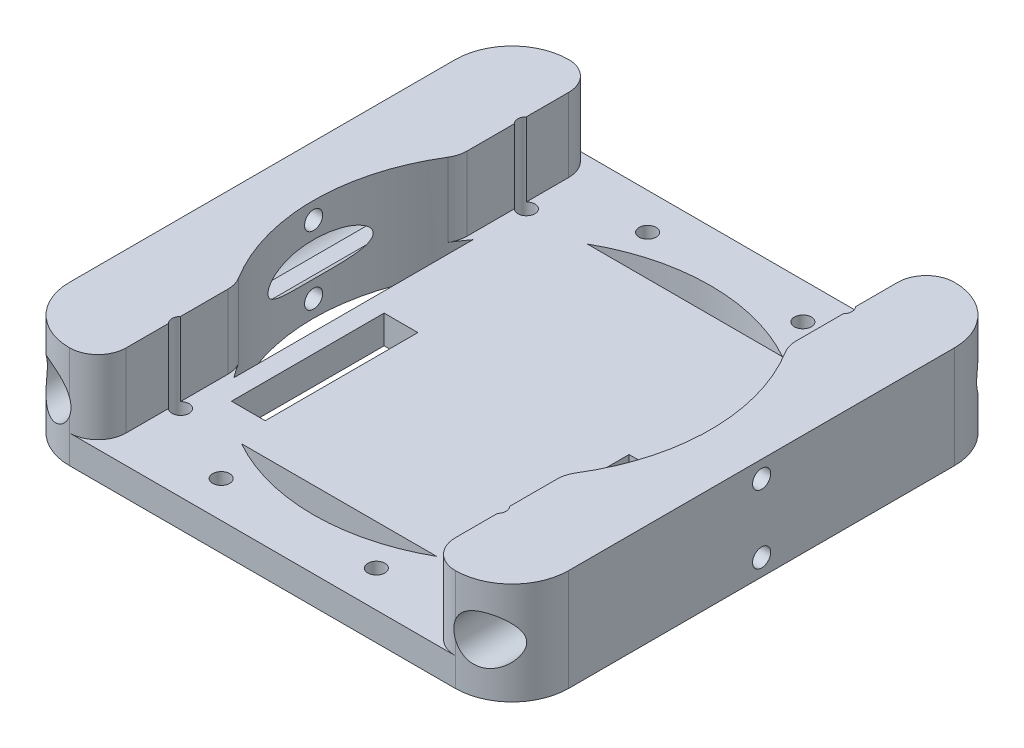
SolidWorks part; units mm, degrees
ref_plane "Front Plane" through (0, 0, 0) normal (0, 0, 1) x (1, 0, 0)
ref_plane "Top Plane" through (0, 0, 0) normal (0, 1, 0) x (1, 0, 0)
ref_plane "Right Plane" through (0, 0, 0) normal (1, 0, 0) x (0, 0, -1)
sketch "Sketch1" plane through (0, 0, 0) normal (0, 1, 0) x (1, 0, 0)
  line L0 (-44, 0) -> (-44, -44) construction
  line L1 (-44, -44) -> (44, -44) construction
  line L2 (44, -44) -> (44, 0) construction
  line L4 (-44, -44) -> (44, -44)
  line L5 (-44, -44) -> (-44, 44)
  line L6 (-44, 44) -> (44, 44)
  line L7 (44, -44) -> (44, 44)
  arc A0 (44, 0) -> (-44, 0) centre (0, 0) ccw construction
  dimension "D1" = 88
extrude "Boss-Extrude1" add sketch "Sketch1" along normal blind 18
sketch "Sketch2" plane through (0, 0, 44) normal (0, 0, 1) x (1, 0, 0)
  line L1 (-1044, 9) -> (48956, 9) construction
  line L2 (0, -1000) -> (0, 49000) construction
  line L3 (-44, 18) -> (-44, 0) construction
  circle A0 centre (-38, 9) radius 4.25
  circle A1 centre (38, 9) radius 4.25
  point P7 (-44, 9)
  dimension "D1" = 8.5
  dimension "D2" = 6
extrude "Cut-Extrude1" cut sketch "Sketch2" against normal through all
fillet "Fillet1" radius 10 4 edges at (44, 9, 44) (-44, 9, 44) (44, 9, -44) (-44, 9, -44)
sketch "Sketch3" plane through (0, 18, 0) normal (0, 1, 0) x (1, 0, 0)
  circle A0 centre (0, 0) radius 35
  dimension "D1" = 70
extrude "Cut-Extrude2" cut sketch "Sketch3" against normal through all
sketch "Sketch5" plane through (0, 0, 0) normal (0, 1, 0) x (1, 0, 0)
  line L0 (-44, 34) -> (-44, -34) construction
  circle A0 centre (0, 0) radius 44
  circle A1 centre (0, 0) radius 35
  circle A3 centre (0, 0) radius 35 construction
extrude "Boss-Extrude2" add sketch "Sketch5" along normal blind 5
sketch "Sketch8" plane through (0, 18, 0) normal (0, 1, 0) x (1, 0, 0)
  line L0 (-34, -44) -> (34, -44) construction
  line L1 (29, 46) -> (-29, 46)
  line L2 (29, 46) -> (29, -46)
  line L3 (29, -46) -> (-29, -46)
  line L4 (-29, 46) -> (-29, -46)
  line L5 (29, 46) -> (-29, -46) construction
  line L6 (29, -46) -> (-29, 46) construction
  point P0 (0, 0)
  point P8 (28.1766, -10.94)
  point P9 (40.6366, 4.14)
  point P11 (0, 0)
  dimension "D1" = 58
  dimension "D2" = 2
extrude "Cut-Extrude4" cut sketch "Sketch8" against normal up to surface (13 mm away) up to face at (-38.0405, 5, 0)
fillet "Fillet2" radius 5 8 edges at (29, 11.5, 44) (29, 11.5, 19.5959) (29, 11.5, -19.5959) (29, 11.5, -44) (-29, 11.5, -44) (-29, 11.5, -19.5959) (-29, 11.5, 19.5959) (-29, 11.5, 44)
sketch "Sketch10" plane through (0, 5, 0) normal (0, 1, 0) x (1, 0, 0)
  line L1 (27.94, -30.48) -> (-27.94, -30.48)
  line L2 (27.94, -30.48) -> (27.94, 30.48)
  line L3 (27.94, 30.48) -> (-27.94, 30.48)
  line L4 (-27.94, -30.48) -> (-27.94, 30.48)
  line L5 (27.94, -30.48) -> (-27.94, 30.48) construction
  line L6 (27.94, 30.48) -> (-27.94, -30.48) construction
  line L7 (-19.12, -24.38) -> (-24.07, -24.38)
  line L8 (-19.12, -24.38) -> (-19.12, 1.53)
  line L9 (-19.12, 1.53) -> (-24.07, 1.53)
  line L10 (-24.07, -24.38) -> (-24.07, 1.53)
  line L11 (-19.12, -24.38) -> (-24.07, 1.53) construction
  line L12 (-19.12, 1.53) -> (-24.07, -24.38) construction
  line L13 (24.06, -24.38) -> (19.11, -24.38)
  line L14 (24.06, -24.38) -> (24.06, 1.53)
  line L15 (24.06, 1.53) -> (19.11, 1.53)
  line L16 (19.11, -24.38) -> (19.11, 1.53)
  line L17 (24.06, -24.38) -> (19.11, 1.53) construction
  line L18 (24.06, 1.53) -> (19.11, -24.38) construction
  point P0 (0, 0)
  point P6 (21.585, -11.425)
  point P7 (-21.595, -11.425)
  dimension "D1" = 55.88
  dimension "D2" = 60.96
  dimension "D3" = 3.87
  dimension "D4" = 4.95
  dimension "D5" = 25.91
  dimension "D6" = 38.23
  dimension "D7" = 6.1
extrude "Boss-Extrude3" add sketch "Sketch10" against normal up to surface (5 mm away) up to face at (0, 0, 0)
sketch "Sketch11" plane through (0, 5, 0) normal (0, 1, 0) x (1, 0, 0)
  line L0 (18.61, 2.03) -> (18.61, -24.88)
  line L1 (-24.07, 1.53) -> (-19.12, 1.53) construction
  line L2 (-24.07, 1.53) -> (-24.07, -24.38) construction
  line L3 (-24.07, -24.38) -> (-19.12, -24.38) construction
  line L4 (-19.12, 1.53) -> (-19.12, -24.38) construction
  line L5 (24.06, 1.53) -> (19.11, 1.53) construction
  line L6 (24.06, 1.53) -> (24.06, -24.38) construction
  line L7 (24.06, -24.38) -> (19.11, -24.38) construction
  line L8 (19.11, 1.53) -> (19.11, -24.38) construction
  line L9 (24.56, -24.88) -> (18.61, -24.88)
  line L10 (24.56, 2.03) -> (24.56, -24.88)
  line L11 (24.56, 2.03) -> (18.61, 2.03)
  line L12 (-24.57, -24.88) -> (-18.62, -24.88)
  line L13 (-18.62, 2.03) -> (-18.62, -24.88)
  line L14 (-24.57, 2.03) -> (-18.62, 2.03)
  line L15 (-24.57, 2.03) -> (-24.57, -24.88)
  line L16 (17.2038, 30.48) -> (-17.2038, 30.48) construction
  line L17 (27.94, -30.48) -> (-27.94, -30.48) construction
  line L18 (27.94, -30.48) -> (27.94, 30.48) construction
  line L19 (27.94, 30.48) -> (-27.94, 30.48) construction
  line L20 (-27.94, -30.48) -> (-27.94, 30.48) construction
  line L21 (27.94, -30.48) -> (-27.94, 30.48) construction
  line L22 (27.94, 30.48) -> (-27.94, -30.48) construction
  line L23 (-27.94, 21.0798) -> (-27.94, -21.0798) construction
  circle A0 centre (-27.94, 30.48) radius 1.5
  circle A1 centre (27.94, 30.48) radius 1.5
  circle A2 centre (-27.94, -30.48) radius 1.5
  circle A3 centre (27.94, -30.48) radius 1.5
  point P20 (0, 0)
  dimension "D3" = 3
  dimension "D1" = 0.5
  dimension "D2" = 0.5
extrude "Cut-Extrude5" cut sketch "Sketch11" against normal through all and the other way through all
sketch "Sketch12" plane through (44, 0, 0) normal (1, 0, 0) x (0, 0, -1)
  line L0 (-34, 0) -> (34, 0) construction
  line L1 (-34, 18) -> (34, 18) construction
  circle A0 centre (0, 15) radius 1.6
  circle A1 centre (0, 3) radius 1.6
  point P4 (0, 0)
  dimension "D1" = 3.2
  dimension "D2" = 3
  dimension "D3" = 3
extrude "Cut-Extrude6" cut sketch "Sketch12" against normal up to next
mirror "Mirror1" about plane through (0, 0, 0) normal (1, 0, 0) of "Cut-Extrude6"
sketch "Sketch13" plane through (0, 5, 0) normal (0, 1, 0) x (1, 0, 0)
  line L0 (0, -1000) -> (0, 49000) construction
  line L1 (-13.6808, 37.5877) -> (0, 0) construction
  circle A0 centre (-13.6808, 37.5877) radius 1.5
  dimension "D1" = 3
  dimension "D2" = 40
  dimension "D3" = 20
extrude "Cut-Extrude7" cut sketch "Sketch13" against normal through all and the other way through all
mirror "Mirror2" about plane through (0, 0, 0) normal (1, 0, 0) of "Cut-Extrude7"
mirror "Mirror3" about plane through (0, 0, 0) normal (0, 0, 1) of "Mirror2", "Cut-Extrude7"
